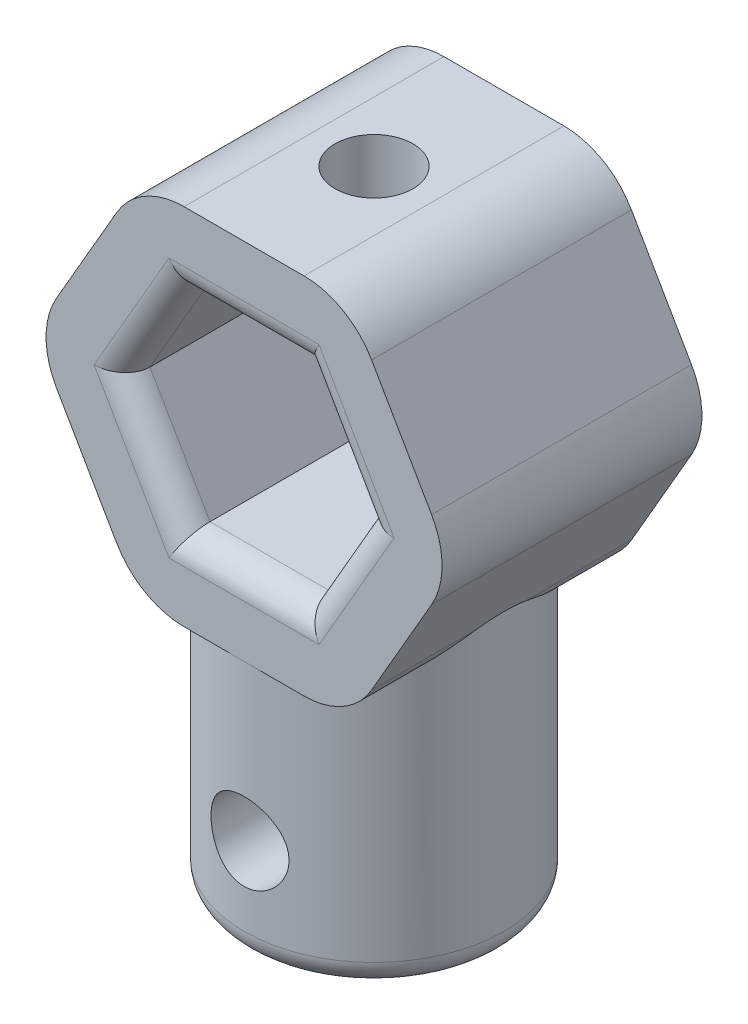
SolidWorks part; units mm, degrees
ref_plane "Plano frontal" through (0, 0, 0) normal (0, 0, 1) x (1, 0, 0)
ref_plane "Plano superior" through (0, 0, 0) normal (0, 1, 0) x (1, 0, 0)
ref_plane "Plano direito" through (0, 0, 0) normal (1, 0, 0) x (0, 0, -1)
sketch "Esboço1" plane through (0, 0, 0) normal (0, 1, 0) x (1, 0, 0)
  circle A0 centre (0, 0) radius 5
  circle A1 centre (0, 0) radius 2.3
  dimension "D1" = 10
  dimension "D2" = 4.6
extrude "Ressalto-extrusão1" add sketch "Esboço1" along normal blind 12
sketch "Esboço2" plane through (0, 0, 0) normal (0, 0, 1) x (1, 0, 0)
  circle A0 centre (0, 4) radius 1.5
  dimension "D1" = 3
  dimension "D2" = 4
extrude "Corte-extrusão1" cut sketch "Esboço2" along normal blind 10
sketch "Esboço3" plane through (0, 0, 0) normal (0, 0, 1) x (1, 0, 0)
  line L0 (5, 12) -> (-5, 12) construction
  line L7 (2.3094, 13) -> (4.6188, 17)
  line L8 (4.6188, 17) -> (2.3094, 21)
  line L9 (2.3094, 21) -> (-2.3094, 21)
  line L10 (-2.3094, 21) -> (-4.6188, 17)
  line L11 (-4.6188, 17) -> (-2.3094, 13)
  line L12 (-2.3094, 13) -> (2.3094, 13)
  line L13 (4.0415, 10) -> (8.0829, 17)
  line L14 (8.0829, 17) -> (4.0415, 24)
  line L15 (4.0415, 24) -> (-4.0415, 24)
  line L16 (-4.0415, 24) -> (-8.0829, 17)
  line L17 (-8.0829, 17) -> (-4.0415, 10)
  line L18 (-4.0415, 10) -> (4.0415, 10)
  circle A0 centre (0, 17) radius 4 construction
  circle A1 centre (0, 17) radius 7 construction
  dimension "D1" = 8
  dimension "D2" = 13
  dimension "D3" = 3
extrude "Ressalto-extrusão2" add sketch "Esboço3" along normal mid plane 10
sketch "Esboço4" plane through (0, 24, 0) normal (0, 1, 0) x (1, 0, 0)
  circle A0 centre (0, 0) radius 1.5
  dimension "D1" = 3
extrude "Corte-extrusão2" cut sketch "Esboço4" against normal blind 5
fillet "Filete1" radius 1 14 edges at (-3.4641, 15, -5) (-3.4641, 19, -5) (0, 21, -5) (3.4641, 19, -5) (0, 13, -5) (3.4641, 15, -5) (0, 21, 5) (-3.4641, 19, 5) (-3.4641, 15, 5) (0, 13, 5) (3.4641, 15, 5) (3.4641, 19, 5) (0, 0, 2.3) (0, 0, 5)
fillet "Filete2" radius 3 8 edges at (-4.0415, 10, -3.972) (-4.0415, 10, 3.972) (8.0829, 17, 0) (4.0415, 10, 3.972) (4.0415, 10, -3.972) (4.0415, 24, 0) (-4.0415, 24, 0) (-8.0829, 17, 0)
